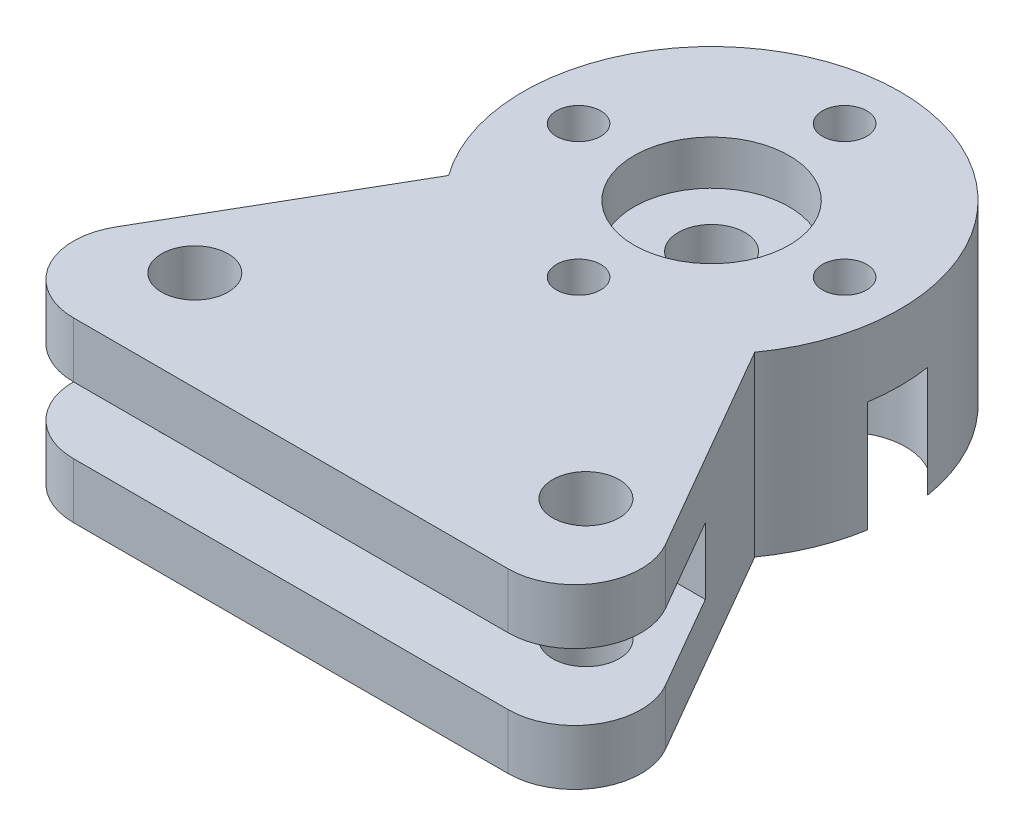
SolidWorks part; units mm, degrees
ref_plane "Front Plane" through (0, 0, 0) normal (0, 0, 1) x (1, 0, 0)
ref_plane "Top Plane" through (0, 0, 0) normal (0, 1, 0) x (1, 0, 0)
ref_plane "Right Plane" through (0, 0, 0) normal (1, 0, 0) x (0, 0, -1)
sketch "Sketch1" plane through (0, 0, 0) normal (0, 1, 0) x (1, 0, 0)
  line L0 (0, 10.3205) -> (0, -4.1695) construction
  line L1 (-2.5981, 12.8205) -> (-12.4019, -4.1603)
  line L2 (-9.8038, -8.6603) -> (9.8038, -8.6603)
  line L3 (12.4019, -4.1603) -> (2.5981, 12.8205)
  circle A0 centre (0, 0) radius 8.6603 construction
  arc A1 (9.8038, -8.6603) -> (12.4019, -4.1603) centre (9.8038, -5.6603) ccw
  arc A2 (-12.4019, -4.1603) -> (-9.8038, -8.6603) centre (-9.8038, -5.6603) ccw
  arc A3 (-2.5981, 12.8205) -> (2.5981, 12.8205) centre (0, 11.3205) cw
  circle A4 centre (0, 10.3205) radius 1.5
  circle A5 centre (-8.8203, -4.1695) radius 1.5
  circle A6 centre (8.8203, -4.1695) radius 1.5
  point P10 (-15, -8.6603)
  point P13 (0, 17.3205)
  dimension "D2" = 3
  dimension "D3" = 3
  dimension "D4" = 3.5
  dimension "D5" = 3.5
  dimension "D7" = 3
  dimension "D1" = 30
  dimension "D6" = 14.49
  dimension "D8" = 8.8203
extrude "Boss-Extrude1" add sketch "Sketch1" along normal blind 8
sketch "Sketch2" plane through (0, 0, 8.6603) normal (0, 0, 1) x (1, 0, 0)
  line L0 (-13.1889, 5.5) -> (-13.1889, 2.5)
  line L1 (-13.1889, 5.5) -> (13.2971, 5.5)
  line L2 (-13.1889, 2.5) -> (13.2971, 2.5)
  line L3 (13.2971, 5.5) -> (13.2971, 2.5)
  line L4 (-9.8038, 8) -> (9.8038, 8) construction
  line L5 (-9.8038, 0) -> (9.8038, 0) construction
  dimension "D1" = 2.5
  dimension "D3" = 2.5
extrude "Cut-Extrude3" cut sketch "Sketch2" against normal blind 8.75
sketch "Sketch3" plane through (0, 0, 0) normal (0, -1, 0) x (-1, 0, 0)
  circle A0 centre (0, 10.3205) radius 8.5
  circle A1 centre (0, 10.3205) radius 1.5
  circle A2 centre (-6, 10.3205) radius 1
  circle A3 centre (6, 10.3205) radius 1
  circle A4 centre (0, 16.3205) radius 1
  circle A5 centre (0, 4.3205) radius 1
  dimension "D1" = 17
  dimension "D2" = 2
  dimension "D3" = 2
  dimension "D4" = 2
  dimension "D5" = 3
  dimension "D6" = 2
  dimension "D7" = 6
  dimension "D8" = 6
extrude "Boss-Extrude2" add sketch "Sketch3" against normal up to surface (8 mm away) contours A5 | A0 | A1 | A2 | A4 | A3 region at (0, 0, -4.3205) up to face at (-8.8203, 8, 5.6695)
sketch "Sketch4" plane through (0, 0, 0) normal (0, -1, 0) x (1, 0, 0)
  line L0 (0, -10.3205) -> (14.6172, -10.3205) construction
  circle A0 centre (-6, -10.3205) radius 2.75
  circle A1 centre (6, -10.3205) radius 2.75
  circle A2 centre (0, -16.3205) radius 2.75
  circle A3 centre (0, -4.3205) radius 2.75
  dimension "D1" = 5.5
  dimension "D2" = 5.5
  dimension "D3" = 5.5
extrude "Cut-Extrude4" cut sketch "Sketch4" against normal blind 5
sketch "Sketch5" plane through (0, 8, 0) normal (0, 1, 0) x (1, 0, 0)
  circle A0 centre (0, 10.3205) radius 3.5
  dimension "D1" = 7
extrude "Cut-Extrude5" cut sketch "Sketch5" against normal blind 2
extrude "Cut-Extrude6" cut sketch "Sketch3<3>" against normal blind 32 contours A5 region at (0, 0, -4.3205)
sketch "Sketch3<3>" plane through (0, 0, 0) normal (0, -1, 0) x (-1, 0, 0) same geometry as "Sketch3"
